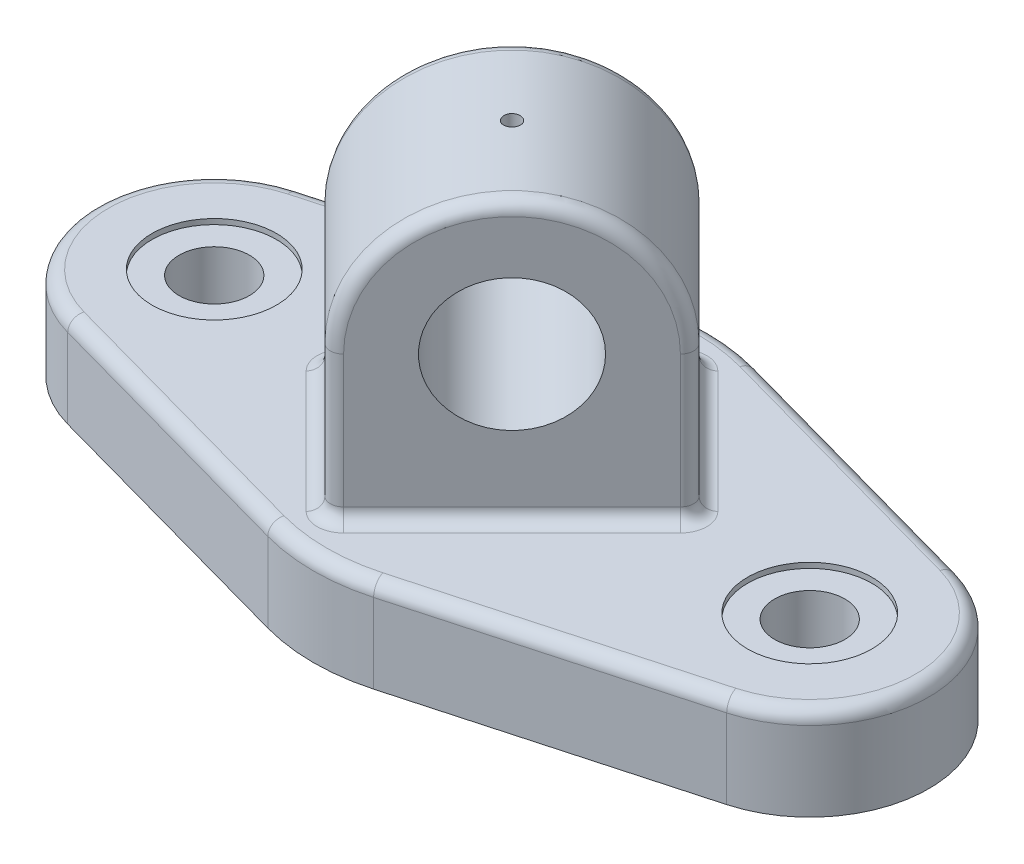
SolidWorks part; units mm, degrees
ref_plane "Front Plane" through (0, 0, 0) normal (0, 0, 1) x (1, 0, 0)
ref_plane "Top Plane" through (0, 0, 0) normal (0, 1, 0) x (1, 0, 0)
ref_plane "Right Plane" through (0, 0, 0) normal (1, 0, 0) x (0, 0, -1)
sketch "Sketch1" plane through (0, 0, 0) normal (0, 1, 0) x (1, 0, 0)
  line L0 (63.246, 22.0322) -> (10.16, 36.7204)
  line L1 (10.16, -36.7204) -> (63.246, -22.0322)
  line L2 (0, -1076.2) -> (0, -38.1) construction
  line L3 (0, 38.1) -> (0, 75.9975) construction
  line L4 (0, -55) -> (0, 55) construction
  line L5 (-10.16, -36.7204) -> (-63.246, -22.0322)
  line L6 (-63.246, 22.0322) -> (-10.16, 36.7204)
  arc A0 (63.246, -22.0322) -> (63.246, 22.0322) centre (57.15, 0) ccw
  arc A1 (-10.16, -36.7204) -> (10.16, -36.7204) centre (0, 0) ccw
  arc A2 (10.16, 36.7204) -> (-10.16, 36.7204) centre (0, 0) ccw
  arc A3 (-63.246, -22.0322) -> (-63.246, 22.0322) centre (-57.15, 0) cw
  dimension "D1" = 76.2
  dimension "D2" = 45.72
  dimension "D3" = 57.15
extrude "Boss-Extrude1" add sketch "Sketch1" along normal blind 17.78
hole_wizard "CBORE for #00 Binding Head Machine Screw1" positions "Sketch2" profile "Sketch3" counterbore size "#00" standard "ANSI Inch" end condition through all
sketch "Sketch2" plane through (0, 17.78, 0) normal (0, 1, 0) x (1, 0, 0)
  line L0 (0, 0) -> (0, 62.2633) construction
  point P0 (-57.15, 0)
  point P2 (57.15, 0)
  dimension "D1" = 114.3
  dimension "D2" = 57.15
sketch "Sketch3" plane through (-57.15, 17.78, 0) normal (1, 0, 0) x (0, 0, 1)
  line L0 (0, 0) -> (0, 17.78)
  line L1 (0, 17.78) -> (6.7437, 17.78)
  line L3 (6.7437, 17.78) -> (6.7437, 1.016)
  line L4 (6.7437, 1.016) -> (11.938, 1.016)
  line L5 (11.938, 1.016) -> (11.938, 0)
  line L7 (11.938, 0) -> (0, 0)
  line L11 (0, -6.35) -> (0, 107.95) construction
  dimension "Thru Hole Dia." = 13.4874
  dimension "Thru Hole Depth" = 17.78
  dimension "C'Bore Dia." = 23.876
  dimension "C'Bore Depth" = 1.016
ref_axis "Axis1" through (0, 18.669, 0) along (0, -1, 0)
ref_plane "Plane1" through (0, 0, 0) normal (0.7071, 0, 0.7071) x (0, -1, 0)
sketch "Sketch4" plane through (0, 0, 0) normal (0.7071, 0, 0.7071) x (0, -1, 0)
  line L1 (-45.72, 25.4) -> (-15.24, 25.4)
  line L2 (-15.24, -18.781) -> (-15.24, 29.1425)
  line L3 (-15.24, -18.781) -> (-15.24, 29.1425) construction
  line L4 (-15.24, 25.4) -> (-15.24, -25.4)
  line L5 (-15.24, -25.4) -> (-45.72, -25.4)
  arc A0 (-45.72, 25.4) -> (-45.72, -25.4) centre (-45.72, 0) ccw
  circle A1 centre (-45.72, 0) radius 12.7
  point P1 (0, 0)
  dimension "D2" = 50.8
  dimension "D3" = 25.4
  dimension "D4" = 30.48
  dimension "D1" = 2.54
extrude "Boss-Extrude2" add sketch "Sketch4" along normal mid plane 38.1
hole_wizard "1/8 (0.125) Diameter Hole1" positions "3DSketch1" profile "Sketch6" hole size "1/8" standard "ANSI Inch" end condition up to next
sketch3d "3DSketch1"
  point P0 (0, 71.12, 0)
  dimension "D1" = 0
  dimension "D2" = 0
sketch "Sketch6" plane through (0, 71.12, 0) normal (1, 0, 0) x (0, 0, 1)
  line L0 (0, 0) -> (0, 12.7)
  line L1 (0, 12.7) -> (1.5875, 12.7)
  line L2 (1.5875, 12.7) -> (1.5875, 0)
  line L5 (1.5875, 0) -> (0, 0)
  line L11 (0, -6.35) -> (0, 107.95) construction
  dimension "Thru Hole Dia." = 3.175
  dimension "Thru Hole Depth" = 12.7
fillet "Fillet1" radius 2.54 18 edges at (17.9605, 17.78, -17.9605) (-17.9605, 17.78, 17.9605) (0, 17.78, -38.1) (36.703, 17.78, -29.3763) (80.01, 17.78, 0) (36.703, 17.78, 29.3763) (0, 17.78, 38.1) (-36.703, 17.78, 29.3763) (-80.01, 17.78, 0) (31.4309, 31.75, -4.4901) (13.4704, 71.12, 13.4704) (4.4901, 31.75, -31.4309) (-31.4309, 31.75, 4.4901) (-36.703, 17.78, -29.3763) (-4.4901, 31.75, 31.4309) (13.4704, 17.78, 13.4704) (-13.4704, 17.78, -13.4704) (-13.4704, 71.12, -13.4704)
